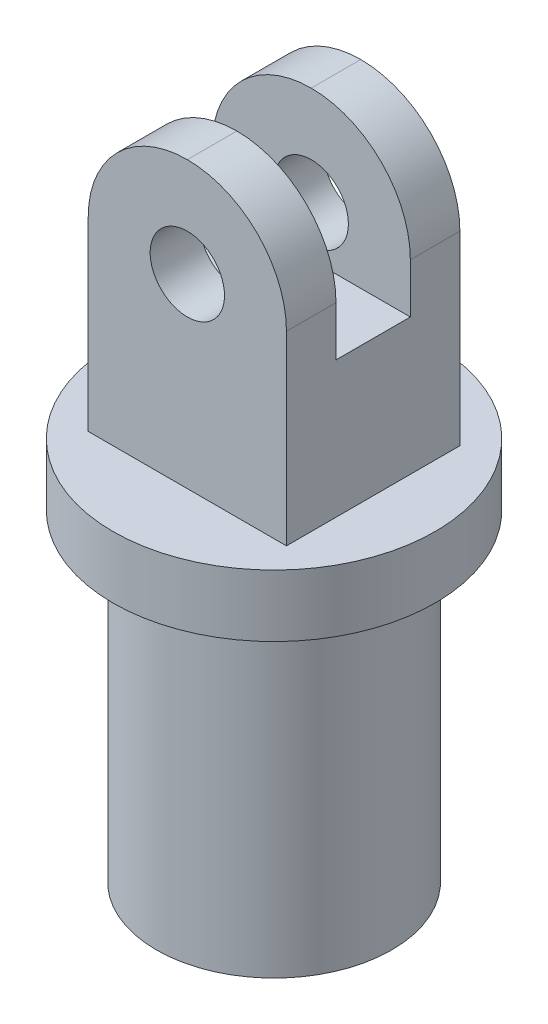
SolidWorks part; units mm, degrees
material "ABS"
ref_plane "Front Plane" through (0, 0, 0) normal (0, 0, 1) x (1, 0, 0)
ref_plane "Top Plane" through (0, 0, 0) normal (0, 1, 0) x (1, 0, 0)
ref_plane "Right Plane" through (0, 0, 0) normal (1, 0, 0) x (0, 0, -1)
sketch "Sketch1" plane through (0, 0, 0) normal (0, 1, 0) x (1, 0, 0)
  circle A0 centre (0, 0) radius 6.5
  dimension "D1" = 13
extrude "Boss-Extrude1" add sketch "Sketch1" along normal blind 2.5
sketch "Sketch2" plane through (0, 0, 0) normal (0, -1, 0) x (1, 0, 0)
  circle A0 centre (0, 0) radius 4.75
  circle A1 centre (0, 0) radius 3
  dimension "D1" = 9.5
  dimension "D2" = 6
extrude "Boss-Extrude2" add sketch "Sketch2" along normal blind 13
sketch "Sketch3" plane through (0, 2.5, 0) normal (0, 1, 0) x (1, 0, 0)
  line L0 (0, 3.5) -> (0, 0) construction
  line L1 (-4, 3.5) -> (4, 3.5)
  line L2 (-4, 3.5) -> (-4, -3.5)
  line L3 (-4, -3.5) -> (4, -3.5)
  line L4 (4, 3.5) -> (4, -3.5)
  line L5 (4, 0) -> (0, 0) construction
  dimension "D1" = 7
  dimension "D2" = 8
extrude "Boss-Extrude3" add sketch "Sketch3" along normal blind 11.5
fillet "Fillet1" radius 4 2 edges at (4, 14, 0) (-4, 14, 0)
sketch "Sketch4" plane through (0, 0, 3.5) normal (0, 0, 1) x (1, 0, 0)
  circle A0 centre (0, 10) radius 1.5
  dimension "D1" = 3
extrude "Cut-Extrude1" cut sketch "Sketch4" against normal blind 13
sketch "Sketch5" plane through (-4, 0, 0) normal (-1, 0, 0) x (0, 0, 1)
  line L0 (0, 8) -> (0, 2.5) construction
  line L1 (1.5, 18.207) -> (-1.5, 18.207)
  line L2 (1.5, 18.207) -> (1.5, 8)
  line L3 (1.5, 8) -> (-1.5, 8)
  line L4 (-1.5, 18.207) -> (-1.5, 8)
  line L5 (-3.5, 2.5) -> (3.5, 2.5) construction
  line L6 (3.5, 10) -> (-3.5, 10) construction
  dimension "D1" = 3
  dimension "D2" = 2
extrude "Cut-Extrude2" cut sketch "Sketch5" against normal blind 13
